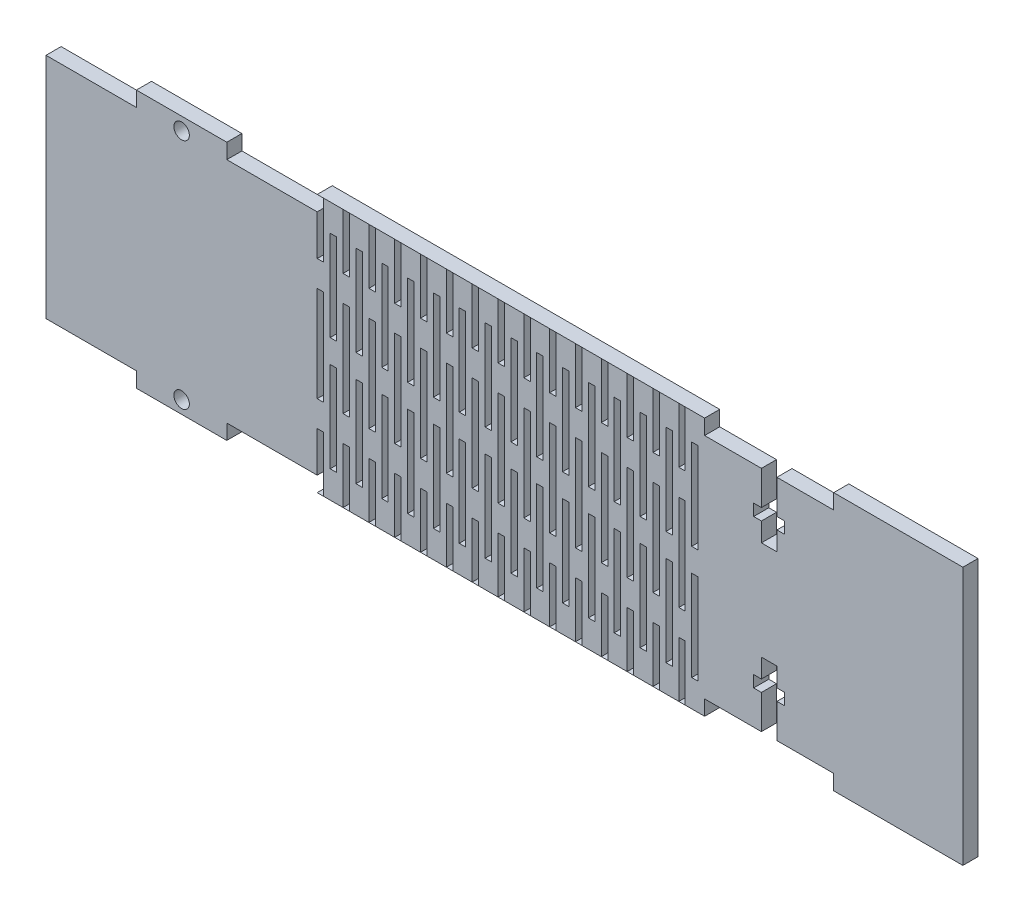
SolidWorks part; units mm, degrees
ref_plane "Front Plane" through (0, 0, 0) normal (0, 0, 1) x (1, 0, 0)
ref_plane "Top Plane" through (0, 0, 0) normal (0, 1, 0) x (1, 0, 0)
ref_plane "Right Plane" through (0, 0, 0) normal (1, 0, 0) x (0, 0, -1)
sketch "Sketch1" plane through (0, 0, 0) normal (0, 0, 1) x (1, 0, 0)
  line L0 (13.97, -25.4) -> (13.97, 25.4)
  line L1 (90.17, 25.4) -> (-90.17, 25.4)
  line L2 (90.17, 25.4) -> (90.17, -25.4)
  line L3 (90.17, -25.4) -> (-90.17, -25.4)
  line L4 (-90.17, 25.4) -> (-90.17, -25.4)
  line L5 (90.17, 25.4) -> (-90.17, -25.4) construction
  line L6 (90.17, -25.4) -> (-90.17, 25.4) construction
  line L7 (-36.83, -25.4) -> (-36.83, 25.4)
  point P0 (0, 0)
  dimension "D1" = 50.8
  dimension "D2" = 180.34
  dimension "D3" = 76.2
  dimension "D4" = 50.8
extrude "Boss-Extrude1" add sketch "Sketch1" along normal blind 2.9718 contours L3 L7 L1 L4 | L7 L3 L0 L1 | L3 L2 L1 L0 region at (-11.43, 0, 0) region at (52.07, 0, 0) region at (-63.5, 0, 0)
sketch "Sketch2" plane through (0, 0, 2.9718) normal (0, 0, 1) x (1, 0, 0)
  line L0 (13.97, 25.3993) -> (13.97, 14.4773)
  line L1 (90.17, -25.4) -> (-90.17, -25.4) construction
  line L2 (90.17, 25.4) -> (-90.17, 25.4) construction
  line L3 (-36.83, -25.4) -> (-36.83, 25.4)
  line L4 (13.97, 25.3993) -> (15.24, 25.3993)
  line L5 (-36.83, 0) -> (112.8347, 0)
  line L6 (12.7, -20.0643) -> (12.7, -2.2843)
  line L7 (11.43, 20.0643) -> (12.7, 20.0643)
  line L8 (11.43, 20.0643) -> (11.43, 2.2843)
  line L9 (11.43, 2.2843) -> (12.7, 2.2843)
  line L10 (12.7, 20.0643) -> (12.7, 2.2843)
  line L11 (11.43, -2.2843) -> (12.7, -2.2843)
  line L12 (11.43, -20.0643) -> (11.43, -2.2843)
  line L13 (11.43, -20.0643) -> (12.7, -20.0643)
  line L14 (8.89, -9.398) -> (8.89, 9.398)
  line L15 (8.89, 25.3993) -> (10.16, 25.3993)
  line L16 (8.89, 25.3993) -> (8.89, 14.4773)
  line L17 (8.89, 14.4773) -> (10.16, 14.4773)
  line L18 (10.16, 25.3993) -> (10.16, 14.4773)
  line L19 (8.89, 9.398) -> (10.16, 9.398)
  line L20 (10.16, 9.398) -> (10.16, -9.398)
  line L21 (8.89, -9.398) -> (10.16, -9.398)
  line L22 (10.16, -25.3993) -> (10.16, -14.4773)
  line L23 (8.89, -14.4773) -> (10.16, -14.4773)
  line L24 (8.89, -25.3993) -> (8.89, -14.4773)
  line L25 (8.89, -25.3993) -> (10.16, -25.3993)
  line L26 (3.81, 25.3993) -> (5.08, 25.3993)
  line L27 (3.81, 25.3993) -> (3.81, 14.4773)
  line L28 (5.08, 25.3993) -> (5.08, 14.4773)
  line L29 (3.81, 14.4773) -> (5.08, 14.4773)
  line L30 (6.35, 20.0643) -> (6.35, 2.2843)
  line L31 (7.62, 20.0643) -> (7.62, 2.2843)
  line L32 (6.35, 20.0643) -> (7.62, 20.0643)
  line L33 (3.81, 9.398) -> (5.08, 9.398)
  line L34 (6.35, 2.2843) -> (7.62, 2.2843)
  line L35 (3.81, -9.398) -> (3.81, 9.398)
  line L36 (5.08, 9.398) -> (5.08, -9.398)
  line L37 (3.81, -9.398) -> (5.08, -9.398)
  line L38 (3.81, -25.3993) -> (3.81, -14.4773)
  line L39 (3.81, -14.4773) -> (5.08, -14.4773)
  line L40 (5.08, -25.3993) -> (5.08, -14.4773)
  line L41 (3.81, -25.3993) -> (5.08, -25.3993)
  line L42 (6.35, -20.0643) -> (6.35, -2.2843)
  line L43 (6.35, -2.2843) -> (7.62, -2.2843)
  line L44 (7.62, -20.0643) -> (7.62, -2.2843)
  line L45 (6.35, -20.0643) -> (7.62, -20.0643)
  line L46 (-1.27, 25.3993) -> (0, 25.3993)
  line L47 (-1.27, 25.3993) -> (-1.27, 14.4773)
  line L48 (0, 25.3993) -> (0, 14.4773)
  line L49 (-1.27, 14.4773) -> (0, 14.4773)
  line L50 (1.27, 20.0643) -> (1.27, 2.2843)
  line L51 (2.54, 20.0643) -> (2.54, 2.2843)
  line L52 (1.27, 20.0643) -> (2.54, 20.0643)
  line L53 (-1.27, 9.398) -> (0, 9.398)
  line L54 (1.27, 2.2843) -> (2.54, 2.2843)
  line L55 (-1.27, -9.398) -> (-1.27, 9.398)
  line L56 (0, 9.398) -> (0, -9.398)
  line L57 (-1.27, -9.398) -> (0, -9.398)
  line L58 (-1.27, -25.3993) -> (-1.27, -14.4773)
  line L59 (-1.27, -14.4773) -> (0, -14.4773)
  line L60 (0, -25.3993) -> (0, -14.4773)
  line L61 (-1.27, -25.3993) -> (0, -25.3993)
  line L62 (1.27, -20.0643) -> (1.27, -2.2843)
  line L63 (1.27, -2.2843) -> (2.54, -2.2843)
  line L64 (2.54, -20.0643) -> (2.54, -2.2843)
  line L65 (1.27, -20.0643) -> (2.54, -20.0643)
  line L66 (-6.35, 25.3993) -> (-5.08, 25.3993)
  line L67 (-6.35, 25.3993) -> (-6.35, 14.4773)
  line L68 (-5.08, 25.3993) -> (-5.08, 14.4773)
  line L69 (-6.35, 14.4773) -> (-5.08, 14.4773)
  line L70 (-3.81, 20.0643) -> (-3.81, 2.2843)
  line L71 (-2.54, 20.0643) -> (-2.54, 2.2843)
  line L72 (-3.81, 20.0643) -> (-2.54, 20.0643)
  line L73 (-6.35, 9.398) -> (-5.08, 9.398)
  line L74 (-3.81, 2.2843) -> (-2.54, 2.2843)
  line L75 (-6.35, -9.398) -> (-6.35, 9.398)
  line L76 (-5.08, 9.398) -> (-5.08, -9.398)
  line L77 (-6.35, -9.398) -> (-5.08, -9.398)
  line L78 (-6.35, -25.3993) -> (-6.35, -14.4773)
  line L79 (-6.35, -14.4773) -> (-5.08, -14.4773)
  line L80 (-5.08, -25.3993) -> (-5.08, -14.4773)
  line L81 (-6.35, -25.3993) -> (-5.08, -25.3993)
  line L82 (-3.81, -20.0643) -> (-3.81, -2.2843)
  line L83 (-3.81, -2.2843) -> (-2.54, -2.2843)
  line L84 (-2.54, -20.0643) -> (-2.54, -2.2843)
  line L85 (-3.81, -20.0643) -> (-2.54, -20.0643)
  line L86 (-11.43, 25.3993) -> (-10.16, 25.3993)
  line L87 (-11.43, 25.3993) -> (-11.43, 14.4773)
  line L88 (-10.16, 25.3993) -> (-10.16, 14.4773)
  line L89 (-11.43, 14.4773) -> (-10.16, 14.4773)
  line L90 (-8.89, 20.0643) -> (-8.89, 2.2843)
  line L91 (-7.62, 20.0643) -> (-7.62, 2.2843)
  line L92 (-8.89, 20.0643) -> (-7.62, 20.0643)
  line L93 (-11.43, 9.398) -> (-10.16, 9.398)
  line L94 (-8.89, 2.2843) -> (-7.62, 2.2843)
  line L95 (-11.43, -9.398) -> (-11.43, 9.398)
  line L96 (-10.16, 9.398) -> (-10.16, -9.398)
  line L97 (-11.43, -9.398) -> (-10.16, -9.398)
  line L98 (-11.43, -25.3993) -> (-11.43, -14.4773)
  line L99 (-11.43, -14.4773) -> (-10.16, -14.4773)
  line L100 (-10.16, -25.3993) -> (-10.16, -14.4773)
  line L101 (-11.43, -25.3993) -> (-10.16, -25.3993)
  line L102 (-8.89, -20.0643) -> (-8.89, -2.2843)
  line L103 (-8.89, -2.2843) -> (-7.62, -2.2843)
  line L104 (-7.62, -20.0643) -> (-7.62, -2.2843)
  line L105 (-8.89, -20.0643) -> (-7.62, -20.0643)
  line L106 (-12.7, -20.0643) -> (-12.7, -2.2843)
  line L107 (-13.97, -2.2843) -> (-12.7, -2.2843)
  line L108 (-13.97, -20.0643) -> (-13.97, -2.2843)
  line L109 (-13.97, -20.0643) -> (-12.7, -20.0643)
  line L110 (-13.97, 20.0643) -> (-13.97, 2.2843)
  line L111 (-12.7, 20.0643) -> (-12.7, 2.2843)
  line L112 (-13.97, 20.0643) -> (-12.7, 20.0643)
  line L113 (-13.97, 2.2843) -> (-12.7, 2.2843)
  line L114 (-16.51, 25.3993) -> (-15.24, 25.3993)
  line L115 (-16.51, 25.3993) -> (-16.51, 14.4773)
  line L116 (-15.24, 25.3993) -> (-15.24, 14.4773)
  line L117 (-16.51, 14.4773) -> (-15.24, 14.4773)
  line L118 (-16.51, -9.398) -> (-16.51, 9.398)
  line L119 (-15.24, 9.398) -> (-15.24, -9.398)
  line L120 (-16.51, 9.398) -> (-15.24, 9.398)
  line L121 (-16.51, -9.398) -> (-15.24, -9.398)
  line L122 (-16.51, -25.3993) -> (-16.51, -14.4773)
  line L123 (-15.24, -25.3993) -> (-15.24, -14.4773)
  line L124 (-16.51, -14.4773) -> (-15.24, -14.4773)
  line L125 (-16.51, -25.3993) -> (-15.24, -25.3993)
  line L126 (-17.78, -20.0643) -> (-17.78, -2.2843)
  line L127 (-19.05, -2.2843) -> (-17.78, -2.2843)
  line L128 (-19.05, -20.0643) -> (-19.05, -2.2843)
  line L129 (-19.05, -20.0643) -> (-17.78, -20.0643)
  line L130 (-19.05, 20.0643) -> (-19.05, 2.2843)
  line L131 (-17.78, 20.0643) -> (-17.78, 2.2843)
  line L132 (-19.05, 20.0643) -> (-17.78, 20.0643)
  line L133 (-19.05, 2.2843) -> (-17.78, 2.2843)
  line L134 (-21.59, 25.3993) -> (-20.32, 25.3993)
  line L135 (-21.59, 25.3993) -> (-21.59, 14.4773)
  line L136 (-20.32, 25.3993) -> (-20.32, 14.4773)
  line L137 (-21.59, 14.4773) -> (-20.32, 14.4773)
  line L138 (-21.59, -9.398) -> (-21.59, 9.398)
  line L139 (-20.32, 9.398) -> (-20.32, -9.398)
  line L140 (-21.59, 9.398) -> (-20.32, 9.398)
  line L141 (-21.59, -9.398) -> (-20.32, -9.398)
  line L142 (-21.59, -25.3993) -> (-21.59, -14.4773)
  line L143 (-20.32, -25.3993) -> (-20.32, -14.4773)
  line L144 (-21.59, -14.4773) -> (-20.32, -14.4773)
  line L145 (-21.59, -25.3993) -> (-20.32, -25.3993)
  line L146 (-22.86, -20.0643) -> (-22.86, -2.2843)
  line L147 (-24.13, -2.2843) -> (-22.86, -2.2843)
  line L148 (-24.13, -20.0643) -> (-24.13, -2.2843)
  line L149 (-24.13, -20.0643) -> (-22.86, -20.0643)
  line L150 (-24.13, 20.0643) -> (-24.13, 2.2843)
  line L151 (-22.86, 20.0643) -> (-22.86, 2.2843)
  line L152 (-24.13, 20.0643) -> (-22.86, 20.0643)
  line L153 (-24.13, 2.2843) -> (-22.86, 2.2843)
  line L154 (-26.67, 25.3993) -> (-25.4, 25.3993)
  line L155 (-26.67, 25.3993) -> (-26.67, 14.4773)
  line L156 (-25.4, 25.3993) -> (-25.4, 14.4773)
  line L157 (-26.67, 14.4773) -> (-25.4, 14.4773)
  line L158 (-26.67, -9.398) -> (-26.67, 9.398)
  line L159 (-25.4, 9.398) -> (-25.4, -9.398)
  line L160 (-26.67, 9.398) -> (-25.4, 9.398)
  line L161 (-26.67, -9.398) -> (-25.4, -9.398)
  line L162 (-26.67, -25.3993) -> (-26.67, -14.4773)
  line L163 (-25.4, -25.3993) -> (-25.4, -14.4773)
  line L164 (-26.67, -14.4773) -> (-25.4, -14.4773)
  line L165 (-26.67, -25.3993) -> (-25.4, -25.3993)
  line L166 (-27.94, -20.0643) -> (-27.94, -2.2843)
  line L167 (-29.21, -2.2843) -> (-27.94, -2.2843)
  line L168 (-29.21, -20.0643) -> (-29.21, -2.2843)
  line L169 (-29.21, -20.0643) -> (-27.94, -20.0643)
  line L170 (-29.21, 20.0643) -> (-29.21, 2.2843)
  line L171 (-27.94, 20.0643) -> (-27.94, 2.2843)
  line L172 (-29.21, 20.0643) -> (-27.94, 20.0643)
  line L173 (-29.21, 2.2843) -> (-27.94, 2.2843)
  line L174 (-31.75, 25.3993) -> (-30.48, 25.3993)
  line L175 (-31.75, 25.3993) -> (-31.75, 14.4773)
  line L176 (-30.48, 25.3993) -> (-30.48, 14.4773)
  line L177 (-31.75, 14.4773) -> (-30.48, 14.4773)
  line L178 (-31.75, -9.398) -> (-31.75, 9.398)
  line L179 (-30.48, 9.398) -> (-30.48, -9.398)
  line L180 (-31.75, 9.398) -> (-30.48, 9.398)
  line L181 (-31.75, -9.398) -> (-30.48, -9.398)
  line L182 (-31.75, -25.3993) -> (-31.75, -14.4773)
  line L183 (-30.48, -25.3993) -> (-30.48, -14.4773)
  line L184 (-31.75, -14.4773) -> (-30.48, -14.4773)
  line L185 (-31.75, -25.3993) -> (-30.48, -25.3993)
  line L186 (-33.02, -20.0643) -> (-33.02, -2.2843)
  line L187 (-34.29, -2.2843) -> (-33.02, -2.2843)
  line L188 (-34.29, -20.0643) -> (-34.29, -2.2843)
  line L189 (-34.29, -20.0643) -> (-33.02, -20.0643)
  line L190 (-34.29, 20.0643) -> (-34.29, 2.2843)
  line L191 (-33.02, 20.0643) -> (-33.02, 2.2843)
  line L192 (-34.29, 20.0643) -> (-33.02, 20.0643)
  line L193 (-34.29, 2.2843) -> (-33.02, 2.2843)
  line L194 (-36.83, 25.3993) -> (-35.56, 25.3993)
  line L195 (-36.83, 25.3993) -> (-36.83, 14.4773)
  line L196 (-35.56, 25.3993) -> (-35.56, 14.4773)
  line L197 (-36.83, 14.4773) -> (-35.56, 14.4773)
  line L198 (-36.83, -9.398) -> (-36.83, 9.398)
  line L199 (-35.56, 9.398) -> (-35.56, -9.398)
  line L200 (-36.83, 9.398) -> (-35.56, 9.398)
  line L201 (-36.83, -9.398) -> (-35.56, -9.398)
  line L202 (-36.83, -25.3993) -> (-36.83, -14.4773)
  line L203 (-35.56, -25.3993) -> (-35.56, -14.4773)
  line L204 (-36.83, -14.4773) -> (-35.56, -14.4773)
  line L205 (-36.83, -25.3993) -> (-35.56, -25.3993)
  line L206 (15.24, 25.3993) -> (15.24, 14.4773)
  line L207 (13.97, 14.4773) -> (15.24, 14.4773)
  line L208 (13.97, 9.398) -> (15.24, 9.398)
  line L209 (13.97, -9.398) -> (13.97, 9.398)
  line L210 (15.24, 9.398) -> (15.24, -9.398)
  line L211 (13.97, -9.398) -> (15.24, -9.398)
  line L212 (13.97, -25.3993) -> (13.97, -14.4773)
  line L213 (13.97, -14.4773) -> (15.24, -14.4773)
  line L214 (15.24, -25.3993) -> (15.24, -14.4773)
  line L215 (13.97, -25.3993) -> (15.24, -25.3993)
  line L216 (16.51, 20.0643) -> (17.78, 20.0643)
  line L217 (16.51, 20.0643) -> (16.51, 2.2843)
  line L218 (17.78, 20.0643) -> (17.78, 2.2843)
  line L219 (16.51, 2.2843) -> (17.78, 2.2843)
  line L220 (16.51, -20.0643) -> (16.51, -2.2843)
  line L221 (16.51, -2.2843) -> (17.78, -2.2843)
  line L222 (17.78, -20.0643) -> (17.78, -2.2843)
  line L223 (16.51, -20.0643) -> (17.78, -20.0643)
  line L224 (19.05, 25.3993) -> (19.05, 14.4773)
  line L225 (19.05, 25.3993) -> (20.32, 25.3993)
  line L226 (20.32, 25.3993) -> (20.32, 14.4773)
  line L227 (19.05, 14.4773) -> (20.32, 14.4773)
  line L228 (19.05, 9.398) -> (20.32, 9.398)
  line L229 (19.05, -9.398) -> (19.05, 9.398)
  line L230 (20.32, 9.398) -> (20.32, -9.398)
  line L231 (19.05, -9.398) -> (20.32, -9.398)
  line L232 (19.05, -25.3993) -> (19.05, -14.4773)
  line L233 (19.05, -14.4773) -> (20.32, -14.4773)
  line L234 (20.32, -25.3993) -> (20.32, -14.4773)
  line L235 (19.05, -25.3993) -> (20.32, -25.3993)
  line L236 (21.59, 20.0643) -> (22.86, 20.0643)
  line L237 (21.59, 20.0643) -> (21.59, 2.2843)
  line L238 (22.86, 20.0643) -> (22.86, 2.2843)
  line L239 (21.59, 2.2843) -> (22.86, 2.2843)
  line L240 (21.59, -20.0643) -> (21.59, -2.2843)
  line L241 (21.59, -2.2843) -> (22.86, -2.2843)
  line L242 (22.86, -20.0643) -> (22.86, -2.2843)
  line L243 (21.59, -20.0643) -> (22.86, -20.0643)
  line L244 (24.13, 25.3993) -> (24.13, 14.4773)
  line L245 (24.13, 25.3993) -> (25.4, 25.3993)
  line L246 (25.4, 25.3993) -> (25.4, 14.4773)
  line L247 (24.13, 14.4773) -> (25.4, 14.4773)
  line L248 (24.13, 9.398) -> (25.4, 9.398)
  line L249 (24.13, -9.398) -> (24.13, 9.398)
  line L250 (25.4, 9.398) -> (25.4, -9.398)
  line L251 (24.13, -9.398) -> (25.4, -9.398)
  line L252 (24.13, -25.3993) -> (24.13, -14.4773)
  line L253 (24.13, -14.4773) -> (25.4, -14.4773)
  line L254 (25.4, -25.3993) -> (25.4, -14.4773)
  line L255 (24.13, -25.3993) -> (25.4, -25.3993)
  line L256 (26.67, 20.0643) -> (27.94, 20.0643)
  line L257 (26.67, 20.0643) -> (26.67, 2.2843)
  line L258 (27.94, 20.0643) -> (27.94, 2.2843)
  line L259 (26.67, 2.2843) -> (27.94, 2.2843)
  line L260 (26.67, -20.0643) -> (26.67, -2.2843)
  line L261 (26.67, -2.2843) -> (27.94, -2.2843)
  line L262 (27.94, -20.0643) -> (27.94, -2.2843)
  line L263 (26.67, -20.0643) -> (27.94, -20.0643)
  line L264 (29.21, 25.3993) -> (29.21, 14.4773)
  line L265 (29.21, 25.3993) -> (30.48, 25.3993)
  line L266 (30.48, 25.3993) -> (30.48, 14.4773)
  line L267 (29.21, 14.4773) -> (30.48, 14.4773)
  line L268 (29.21, 9.398) -> (30.48, 9.398)
  line L269 (29.21, -9.398) -> (29.21, 9.398)
  line L270 (30.48, 9.398) -> (30.48, -9.398)
  line L271 (29.21, -9.398) -> (30.48, -9.398)
  line L272 (29.21, -25.3993) -> (29.21, -14.4773)
  line L273 (29.21, -14.4773) -> (30.48, -14.4773)
  line L274 (30.48, -25.3993) -> (30.48, -14.4773)
  line L275 (29.21, -25.3993) -> (30.48, -25.3993)
  line L276 (31.75, 20.0643) -> (33.02, 20.0643)
  line L277 (31.75, 20.0643) -> (31.75, 2.2843)
  line L278 (33.02, 20.0643) -> (33.02, 2.2843)
  line L279 (31.75, 2.2843) -> (33.02, 2.2843)
  line L280 (31.75, -20.0643) -> (31.75, -2.2843)
  line L281 (31.75, -2.2843) -> (33.02, -2.2843)
  line L282 (33.02, -20.0643) -> (33.02, -2.2843)
  line L283 (31.75, -20.0643) -> (33.02, -20.0643)
  line L284 (34.29, 25.3993) -> (34.29, 14.4773)
  line L285 (34.29, 25.3993) -> (35.56, 25.3993)
  line L286 (35.56, 25.3993) -> (35.56, 14.4773)
  line L287 (34.29, 14.4773) -> (35.56, 14.4773)
  line L288 (34.29, 9.398) -> (35.56, 9.398)
  line L289 (34.29, -9.398) -> (34.29, 9.398)
  line L290 (35.56, 9.398) -> (35.56, -9.398)
  line L291 (34.29, -9.398) -> (35.56, -9.398)
  line L292 (34.29, -25.3993) -> (34.29, -14.4773)
  line L293 (34.29, -14.4773) -> (35.56, -14.4773)
  line L294 (35.56, -25.3993) -> (35.56, -14.4773)
  line L295 (34.29, -25.3993) -> (35.56, -25.3993)
  line L296 (36.83, 20.0643) -> (38.1, 20.0643)
  line L297 (36.83, 20.0643) -> (36.83, 2.2843)
  line L298 (38.1, 20.0643) -> (38.1, 2.2843)
  line L299 (36.83, 2.2843) -> (38.1, 2.2843)
  line L300 (36.83, -20.0643) -> (36.83, -2.2843)
  line L301 (36.83, -2.2843) -> (38.1, -2.2843)
  line L302 (38.1, -20.0643) -> (38.1, -2.2843)
  line L303 (36.83, -20.0643) -> (38.1, -20.0643)
  point P30 (8.89, 0)
  point P31 (10.16, 0)
  dimension "D2" = 6
  dimension "D3" = 1.27
  dimension "D4" = 17.78
  dimension "D6" = 1.27
  dimension "D7" = 10.922
  dimension "D8" = 1.27
  dimension "D9" = 1.27
  dimension "D10" = 9.398
  dimension "D12" = 6
  dimension "D11" = 5
extrude "Cut-Extrude1" cut sketch "Sketch2" against normal blind 2.9718 contours L10 L7 L8 L9 | L18 L15 L16 L17 | L20 L19 L14 L5 | L14 L21 L20 L5 | L12 L13 L6 L11 | L24 L25 L22 L23 | L30 L34 L31 L32 | L42 L45 L44 L43 | L27 L29 L28 L26 | L36 L33 L35 L5 | L35 L37 L36 L5 | L38 L41 L40 L39 | L50 L54 L51 L52 | L62 L65 L64 L63 | L47 L49 L48 L46 | L56 L53 L55 L5 | L55 L57 L56 L5 | L58 L61 L60 L59 | L70 L74 L71 L72 | L82 L85 L84 L83 | L67 L69 L68 L66 | L76 L73 L75 L5 | L75 L77 L76 L5 | L78 L81 L80 L79 | L90 L94 L91 L92 | L102 L105 L104 L103 | L87 L89 L88 L86 | L96 L93 L95 L5 | L95 L97 L96 L5 | L98 L101 L100 L99 | L110 L113 L111 L112 | L115 L117 L116 L114 | L120 L118 L5 L119 | L118 L121 L119 L5 | L108 L109 L106 L107 | L130 L133 L131 L132 | L122 L125 L123 L124 | L128 L129 L126 L127 | L135 L137 L136 L134 | L140 L138 L5 L139 | L138 L141 L139 L5 | L142 L145 L143 L144 | L148 L149 L146 L147 | L150 L153 L151 L152 | L155 L157 L156 L154 | L160 L158 L5 L159 | L158 L161 L159 L5 | L162 L165 L163 L164 | L170 L173 L171 L172 | L168 L169 L166 L167 | L175 L177 L176 L174 | L180 L178 L5 L179 | L178 L181 L179 L5 | L182 L185 L183 L184 | L190 L193 L191 L192 | L188 L189 L186 L187 | L3 L197 L196 L194 | L200 L3 L5 L199 | L3 L201 L199 L5 | L3 L205 L203 L204 | L0 L207 L206 L4 | L210 L208 L209 L5 | L209 L211 L210 L5 | L212 L215 L214 L213 | L217 L219 L218 L216 | L220 L223 L222 L221 | L224 L227 L226 L225 | L230 L228 L229 L5 | L232 L235 L234 L233 | L229 L231 L230 L5 | L237 L239 L238 L236 | L240 L243 L242 L241 | L244 L247 L246 L245 | L250 L248 L249 L5 | L249 L251 L250 L5 | L252 L255 L254 L253 | L257 L259 L258 L256 | L260 L263 L262 L261 | L264 L267 L266 L265 | L270 L268 L269 L5 | L272 L275 L274 L273 | L269 L271 L270 L5 | L280 L283 L282 L281 | L277 L279 L278 L276 | L284 L287 L286 L285 | L290 L288 L289 L5 | L289 L291 L290 L5 | L292 L295 L294 L293 | L297 L299 L298 L296 | L300 L303 L302 L301 region at (14.605, 19.9383, 2.9718) region at (-36.195, 19.9383, 2.9718) region at (34.925, 4.699, 2.9718) region at (34.925, -4.699, 2.9718) region at (29.845, 4.699, 2.9718) region at (29.845, -4.699, 2.9718) region at (24.765, 4.699, 2.9718) region at (24.765, -4.699, 2.9718) region at (19.685, 4.699, 2.9718) region at (19.685, -4.699, 2.9718) region at (14.605, 4.699, 2.9718) region at (14.605, -4.699, 2.9718) region at (9.525, 4.699, 2.9718) region at (9.525, -4.699, 2.9718) region at (4.445, 4.699, 2.9718) region at (4.445, -4.699, 2.9718) region at (-0.635, 4.699, 2.9718) region at (-0.635, -4.699, 2.9718) region at (-5.715, 4.699, 2.9718) region at (-5.715, -4.699, 2.9718) region at (-10.795, 4.699, 2.9718) region at (-10.795, -4.699, 2.9718) region at (-15.875, 4.699, 2.9718) region at (-15.875, -4.699, 2.9718) region at (-20.955, 4.699, 2.9718) region at (-20.955, -4.699, 2.9718) region at (-26.035, 4.699, 2.9718) region at (-26.035, -4.699, 2.9718) region at (-31.115, 4.699, 2.9718) region at (-31.115, -4.699, 2.9718) region at (-36.195, -4.699, 2.9718) region at (-36.195, -19.9383, 2.9718) region at (-36.195, 4.699, 2.9718) region at (12.065, -11.1743, 2.9718) region at (12.065, 11.1743, 2.9718) region at (9.525, 19.9383, 2.9718) region at (9.525, -19.9383, 2.9718) region at (4.445, 19.9383, 2.9718) region at (6.985, 11.1743, 2.9718) region at (4.445, -19.9383, 2.9718) region at (6.985, -11.1743, 2.9718) region at (-0.635, 19.9383, 2.9718) region at (1.905, 11.1743, 2.9718) region at (-0.635, -19.9383, 2.9718) region at (1.905, -11.1743, 2.9718) region at (-5.715, 19.9383, 2.9718) region at (-3.175, 11.1743, 2.9718) region at (-5.715, -19.9383, 2.9718) region at (-3.175, -11.1743, 2.9718) region at (-10.795, 19.9383, 2.9718) region at (-8.255, 11.1743, 2.9718) region at (-10.795, -19.9383, 2.9718) region at (-8.255, -11.1743, 2.9718) region at (-13.335, -11.1743, 2.9718) region at (-13.335, 11.1743, 2.9718) region at (-15.875, 19.9383, 2.9718) region at (-15.875, -19.9383, 2.9718) region at (-18.415, -11.1743, 2.9718) region at (-18.415, 11.1743, 2.9718) region at (-20.955, 19.9383, 2.9718)
sketch "Sketch3" plane through (0, 0, 2.9718) normal (0, 0, 1) x (1, 0, 0)
  line L0 (13.97, 22.4282) -> (13.97, -25.4)
  line L1 (90.17, 25.4) -> (-90.17, 25.4) construction
  line L2 (90.17, -25.4) -> (-90.17, -25.4) construction
  line L3 (90.17, 25.4) -> (90.17, -25.4) construction
  line L7 (64.7598, -22.4282) -> (64.7598, -50.8163)
  line L8 (39.3687, 22.4282) -> (39.3687, 25.4)
  line L13 (39.3687, -22.4282) -> (64.7598, -22.4282)
  line L14 (1.6345, 0) -> (-1.6345, 0) construction
  line L15 (39.3687, -50.8163) -> (39.3687, -22.4282)
  line L17 (13.97, -25.4) -> (13.97, -22.4282)
  line L20 (64.7598, -50.8163) -> (39.3687, -50.8163)
  line L24 (-90.17, 22.4282) -> (-90.17, 50.8163)
  line L25 (-90.17, 25.4) -> (-90.17, -25.4) construction
  line L26 (-90.17, 50.8163) -> (-72.39, 50.8163)
  line L27 (-72.39, 50.8163) -> (-72.39, 22.4282)
  line L28 (-72.39, 22.4282) -> (-90.17, 22.4282)
  line L29 (-54.61, 22.4282) -> (-54.61, 50.8163)
  line L30 (-54.61, 50.8163) -> (-36.83, 50.8163)
  line L31 (-36.83, 50.8163) -> (-36.83, 22.4282)
  line L32 (-36.83, 22.4282) -> (-54.61, 22.4282)
  line L33 (-36.83, -22.4282) -> (-54.61, -22.4282)
  line L34 (-36.83, -50.8163) -> (-36.83, -22.4282)
  line L35 (-54.61, -50.8163) -> (-36.83, -50.8163)
  line L36 (-54.61, -22.4282) -> (-54.61, -50.8163)
  line L37 (-72.39, -22.4282) -> (-90.17, -22.4282)
  line L38 (-72.39, -50.8163) -> (-72.39, -22.4282)
  line L39 (-90.17, -50.8163) -> (-72.39, -50.8163)
  line L40 (-90.17, -22.4282) -> (-90.17, -50.8163)
  line L42 (39.3687, 22.4282) -> (39.3687, 25.4)
  line L46 (39.3687, 25.4) -> (64.7598, 25.4)
  line L47 (39.3687, 25.4) -> (64.7598, 25.4)
  line L50 (90.17, 22.4282) -> (90.17, 19.7125)
  line L54 (39.3687, 25.4) -> (64.7598, 25.4)
  line L55 (39.3687, 22.4282) -> (64.7598, 22.4282)
  line L56 (64.7598, 22.4282) -> (64.7598, 50.8163)
  line L57 (64.7598, 50.8163) -> (39.3687, 50.8163)
  line L58 (39.3687, 50.8163) -> (39.3687, 22.4282)
  line L59 (64.7598, 22.4282) -> (39.3687, 22.4282)
  dimension "D1" = 76.2
  dimension "D3" = 17.78
  dimension "D4" = 17.78
  dimension "D5" = 17.78
extrude "Cut-Extrude3" cut sketch "Sketch3" against normal blind 2.9718 contours L28 L27 L26 L24 | L32 L31 L30 L29 | L37 L40 L39 L38 | L33 L36 L35 L34 | L0 L8 | L0 L17 | L55 L56 L46 L8 | L20 L7 L13 L15 region at (52.0642, -36.6222, 2.9718) region at (52.0642, 23.9141, 2.9718) region at (-81.28, 36.6222, 2.9718) region at (-45.72, 36.6222, 2.9718) region at (-45.72, -36.6222, 2.9718) region at (-81.28, -36.6222, 2.9718)
sketch "Sketch5" plane through (0, 0, 2.9718) normal (0, 0, 1) x (1, 0, 0)
  line L0 (52.0642, 22.4282) -> (52.0642, -46.4437) construction
  line L1 (39.3687, 22.4282) -> (64.7598, 22.4282) construction
  line L2 (53.5882, 22.4282) -> (53.5882, 15.7441)
  line L3 (53.5882, 15.7441) -> (55.1122, 15.7441)
  line L4 (55.1122, 15.7441) -> (55.1122, 13.4581)
  line L5 (55.1122, 13.4581) -> (53.5882, 13.4581)
  line L6 (53.5882, 13.4581) -> (53.5882, 9.7282)
  line L7 (53.5882, 9.7282) -> (50.5402, 9.7282)
  line L8 (50.5402, 13.4581) -> (50.5402, 9.7282)
  line L9 (49.0162, 13.4581) -> (50.5402, 13.4581)
  line L10 (49.0162, 15.7441) -> (49.0162, 13.4581)
  line L11 (50.5402, 15.7441) -> (49.0162, 15.7441)
  line L12 (50.5402, 22.4282) -> (50.5402, 15.7441)
  line L13 (1.6345, 0) -> (-1.6345, 0) construction
  line L14 (50.5402, -22.4282) -> (50.5402, -15.7441)
  line L15 (50.5402, -15.7441) -> (49.0162, -15.7441)
  line L16 (49.0162, -15.7441) -> (49.0162, -13.4581)
  line L17 (49.0162, -13.4581) -> (50.5402, -13.4581)
  line L18 (50.5402, -13.4581) -> (50.5402, -9.7282)
  line L19 (53.5882, -9.7282) -> (50.5402, -9.7282)
  line L20 (53.5882, -13.4581) -> (53.5882, -9.7282)
  line L21 (55.1122, -13.4581) -> (53.5882, -13.4581)
  line L22 (55.1122, -15.7441) -> (55.1122, -13.4581)
  line L23 (53.5882, -15.7441) -> (55.1122, -15.7441)
  line L24 (53.5882, -22.4282) -> (53.5882, -15.7441)
  line L25 (-63.5, 25.4) -> (-63.5, -33.5025)
  line L26 (-54.61, 25.4) -> (-72.39, 25.4) construction
  line L27 (50.5402, 22.4282) -> (53.5882, 22.4282)
  line L28 (50.5402, -22.4282) -> (53.5882, -22.4282)
  line L29 (-90.17, 22.4282) -> (-90.17, -22.4282) construction
  circle A0 centre (-63.5, 22.8881) radius 1.524
  circle A1 centre (-63.5, -22.8881) radius 1.524
  point P12 (52.0642, 9.7282)
  point P31 (52.0642, -9.7282)
  dimension "D6" = 26.67
  dimension "D1" = 3.048
  dimension "D2" = 2.286
  dimension "D3" = 3.048
  dimension "D4" = 6.096
  dimension "D5" = 12.7
  dimension "D7" = 26.67
extrude "Cut-Extrude4" cut sketch "Sketch5" against normal blind 2.9718 contours L0 L27 L12 L11 L10 L9 L8 L7 | L27 L0 L7 L6 L5 L4 L3 L2 | L0 L19 L18 L17 L16 L15 L14 L28 | L19 L0 L28 L24 L23 L22 L21 L20 | A0 | A1 region at (53.0587, 15.8529, 2.9718) region at (51.0698, 15.8529, 2.9718) region at (53.0587, -15.8529, 2.9718) region at (51.0698, -15.8529, 2.9718)
